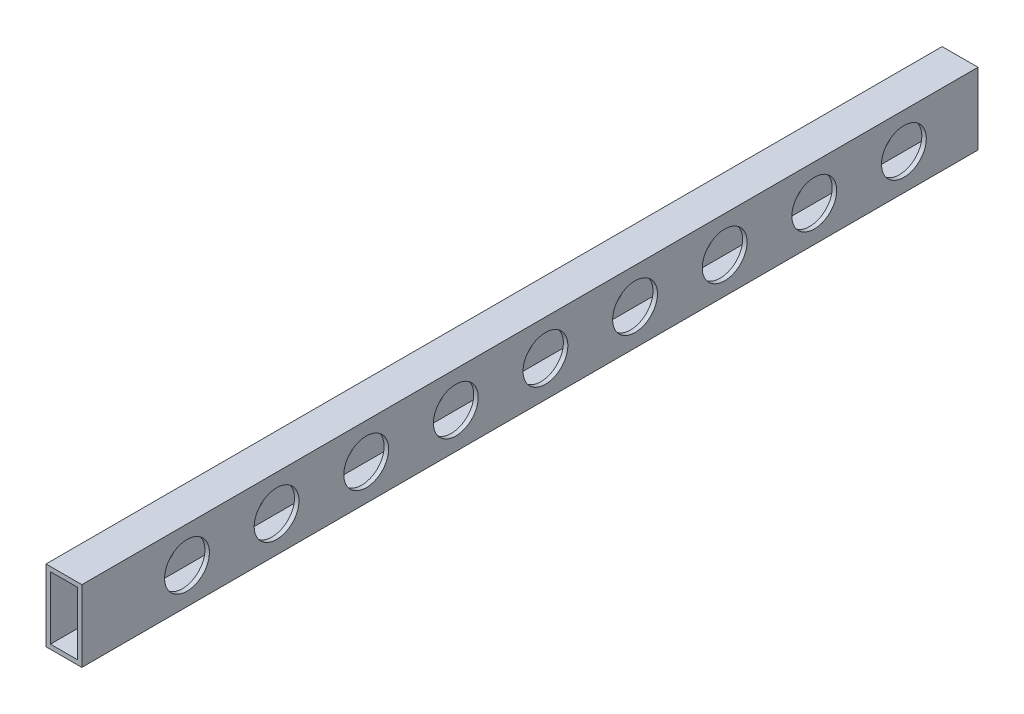
SolidWorks part; units mm, degrees
ref_plane "Front Plane" through (0, 0, 0) normal (0, 0, 1) x (1, 0, 0)
ref_plane "Top Plane" through (0, 0, 0) normal (0, 1, 0) x (1, 0, 0)
ref_plane "Right Plane" through (0, 0, 0) normal (1, 0, 0) x (0, 0, -1)
sketch "Sketch1" plane through (0, 0, 0) normal (0, 0, 1) x (1, 0, 0)
  line L1 (-12.7, -25.4) -> (12.7, -25.4)
  line L2 (-12.7, -25.4) -> (-12.7, 25.4)
  line L3 (-12.7, 25.4) -> (12.7, 25.4)
  line L4 (12.7, -25.4) -> (12.7, 25.4)
  line L5 (-12.7, -25.4) -> (12.7, 25.4) construction
  line L6 (-12.7, 25.4) -> (12.7, -25.4) construction
  line L7 (-9.525, -22.225) -> (9.525, -22.225)
  line L8 (-9.525, -22.225) -> (-9.525, 22.225)
  line L9 (-9.525, 22.225) -> (9.525, 22.225)
  line L10 (9.525, -22.225) -> (9.525, 22.225)
  line L11 (-9.525, -22.225) -> (9.525, 22.225) construction
  line L12 (-9.525, 22.225) -> (9.525, -22.225) construction
  point P0 (0, 0)
  point P1 (0, 0)
  point P7 (0, 0)
  dimension "D1" = 25.4
  dimension "D2" = 50.8
  dimension "D3" = 3.175
  dimension "D4" = 3.175
extrude "Boss-Extrude1" add sketch "Sketch1" along normal blind 635
sketch "Sketch2" plane through (12.7, 0, 0) normal (1, 0, 0) x (0, 0, -1)
  line L1 (-635, -25.4) -> (-635, 25.4) construction
  circle A0 centre (-560.5018, 0) radius 15.875
  circle A1 centre (-497.0018, 0) radius 15.875
  circle A2 centre (-433.5018, 0) radius 15.875
  circle A3 centre (-370.0018, 0) radius 15.875
  circle A4 centre (-306.5018, 0) radius 15.875
  circle A5 centre (-243.0018, 0) radius 15.875
  circle A6 centre (-179.5018, 0) radius 15.875
  circle A7 centre (-116.0018, 0) radius 15.875
  circle A8 centre (-52.5018, 0) radius 15.875
  dimension "D1" = 31.75
  dimension "D2" = 74.4982
  dimension "D3" = 9
extrude "Cut-Extrude1" cut sketch "Sketch2" against normal up to surface (25.4 mm away) up to face at (-12.7, 0, 317.5)
